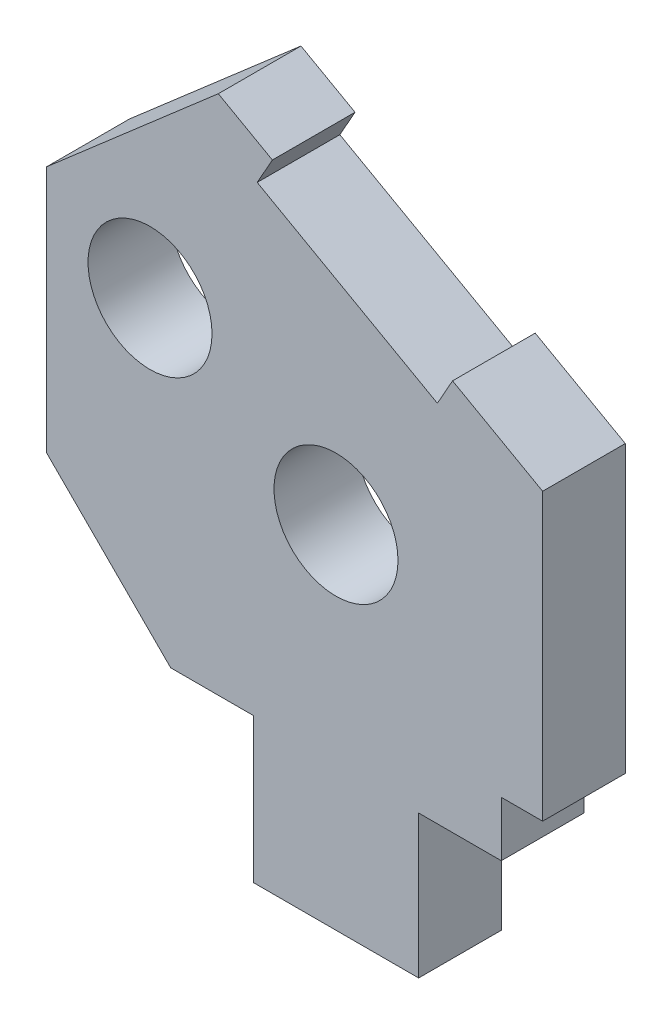
SolidWorks part; units mm, degrees
material "6061 合金"
ref_plane "前视基准面" through (0, 0, 0) normal (0, 0, 1) x (1, 0, 0)
ref_plane "上视基准面" through (0, 0, 0) normal (0, 1, 0) x (1, 0, 0)
ref_plane "右视基准面" through (0, 0, 0) normal (1, 0, 0) x (0, 0, -1)
sketch "草图1" plane through (0, 0, 0) normal (0, 0, 1) x (1, 0, 0)
  line L1 (-10, 25) -> (-1.6948, 32.2127)
  line L2 (14, 23.3994) -> (14, 9.5727)
  line L4 (-1.6948, 32.2127) -> (0.921, 30.7438)
  line L5 (-10, 25) -> (-10, 13)
  line L6 (-10, 13) -> (-4, 13)
  line L7 (14, 9.5727) -> (12, 9.5727)
  line L8 (12, 9.5727) -> (12, 6.9151)
  line L14 (-4, 7) -> (-4, 13)
  line L15 (0.921, 30.7438) -> (0.1866, 29.4359)
  line L16 (0.1866, 29.4359) -> (8.9059, 24.5396)
  line L17 (8.9059, 24.5396) -> (9.6403, 25.8475)
  line L18 (9.6403, 25.8475) -> (14, 23.3994)
  line L19 (-4, 7) -> (0, 7)
  line L20 (0, 7) -> (0, 0)
  line L21 (0, 0) -> (8, 0)
  line L22 (8, 0) -> (8, 6.9151)
  line L23 (8, 6.9151) -> (12, 6.9151)
  circle A0 centre (-5, 22) radius 3
  circle A1 centre (4, 17) radius 3
  dimension "D4" = 6
  dimension "D7" = 6
  dimension "D8" = 6
  dimension "D1" = 11
  dimension "D2" = 18
  dimension "D3" = 4
  dimension "D5" = 12
  dimension "D6" = 14
  dimension "D9" = 7
  dimension "D10" = 5
  dimension "D11" = 2
  dimension "D12" = 8
  dimension "D13" = 4
  dimension "D14" = 9
  dimension "D15" = 4
  dimension "D18" = 1.5
  dimension "D19" = 10
  dimension "D20" = 5
extrude "凸台-拉伸1" add sketch "草图1" along normal blind 4
chamfer "倒角1" distance 6 angle 45 1 edges at (-4, 13, 2)
